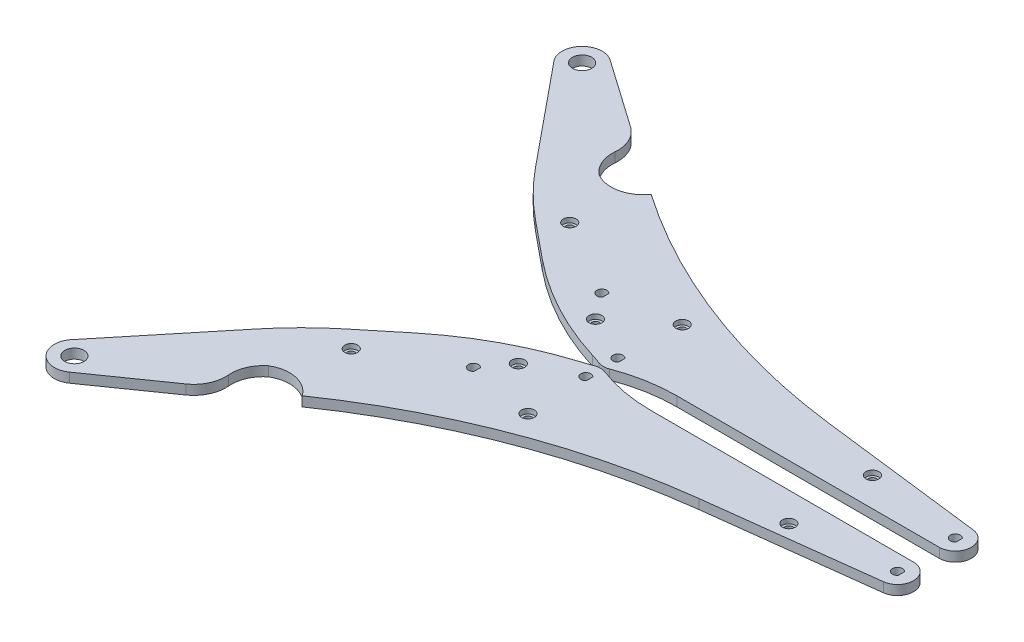
SolidWorks part; units mm, degrees
ref_plane "前视基准面" through (0, 0, 0) normal (0, 0, 1) x (1, 0, 0)
ref_plane "上视基准面" through (0, 0, 0) normal (0, 1, 0) x (1, 0, 0)
ref_plane "右视基准面" through (0, 0, 0) normal (1, 0, 0) x (0, 0, -1)
other "Configuration Table"
sketch "草图3" plane through (0, 0, 0) normal (0, 1, 0) x (1, 0, 0)
  line L0 (0, 0) -> (100, 0)
  line L1 (-82.5612, -80.1259) -> (0, -22.316)
  line L2 (-90.5752, -70.5752) -> (-141.151, -121.151) construction
  line L3 (100.6093, -9.9627) -> (0, -22.316)
  line L4 (-141.151, -121.151) -> (-82.5612, -80.1259) construction
  line L5 (100, 0) -> (181.7493, 0) construction
  line L6 (181.7493, 0) -> (100.6093, -9.9627) construction
  line L7 (101.2, -4.0189) -> (101.2, -5.9811)
  line L8 (-19.8, -15.0189) -> (-19.8, -16.9811)
  line L9 (0.2, -0.0189) -> (0.2, -1.9811)
  line L10 (-20, 0) -> (-90.5752, -70.5752)
  line L11 (-53.0717, -59.4772) -> (-58.8074, -51.2857)
  line L12 (0, 0) -> (-20, 0)
  line L13 (-58.8074, -51.2857) -> (-45.701, -42.1085)
  line L14 (-45.701, -42.1085) -> (-39.9652, -50.3)
  line L16 (-90.5752, -70.5752) -> (-58.8231, -31.7521)
  line L17 (-58.8231, -31.7521) -> (-20, 0)
  circle A0 centre (100, -5) radius 1.55
  circle A1 centre (100, -5) radius 5
  circle A2 centre (-86.1504, -75) radius 6.2576
  circle A3 centre (-1, -1) radius 1.55
  circle A4 centre (-1, -1) radius 4.55
  circle A5 centre (-21, -16) radius 1.55
  circle A6 centre (-86.1504, -75) radius 3
  dimension "D2" = 10
  dimension "D3" = 3.1
  dimension "D10" = 75
  dimension "D11" = 3.1
  dimension "D12" = 3
  dimension "D13" = 3.1
  dimension "D16" = 6
  dimension "D1" = 100
  dimension "D4" = 7
  dimension "D5" = 135
  dimension "D6" = 20
  dimension "D7" = 10
  dimension "D8" = 1
  dimension "D9" = 1
  dimension "D14" = 15
  dimension "D15" = 20
  dimension "D17" = 1.2
  dimension "D18" = 1.2
  dimension "D19" = 1.2
  dimension "D20" = 10
  dimension "D21" = 16
  dimension "D22" = 36
  dimension "D23" = 5
extrude "凸台-拉伸1" add sketch "草图3" along normal blind 3 contours A4 L12 L10 A2 L1 L3 A1 L0 A5 | A2 A6 | L8 A5 | L0 A4 L12 A3 | L9 A3 | L12 A4 L0 A3 | A1 A0 | L7 A0 | L17 L16 L10 region at (-1, 0, -1.5321) region at (-1, 0, 2.6387) region at (-3.2868, 0, 23.095) region at (0.3414, 0, 1) region at (103.4355, 0, 1.5645) region at (-56.4661, 0, 34.1091) region at (-83.8234, 0, 69.3822) region at (101.3414, 0, 5) region at (-19.6586, 0, 16)
fillet "圆角1" radius 200 1 edges at (0, 1.5, 22.316)
fillet "圆角3" radius 50 2 edges at (3.4387, 1.5, 0) (-5.4387, 1.5, 0)
sketch "草图4" plane through (0, 3, 0) normal (0, 1, 0) x (1, 0, 0)
  circle A0 centre (70.2, -9) radius 2
  circle A1 centre (70.2, -9) radius 1.25
  circle A2 centre (0, -20) radius 2
  circle A3 centre (0, -20) radius 1.25
  circle A8 centre (-45, -30) radius 2
  circle A9 centre (-45, -30) radius 1.25
  circle A10 centre (-15, -8) radius 2
  circle A11 centre (-15, -8) radius 1.25
  dimension "D1" = 4
  dimension "D2" = 2.5
  dimension "D3" = 70
  dimension "D4" = 9
  dimension "D5" = 20
  dimension "D6" = 15
  dimension "D7" = 8
  dimension "D8" = 45
  dimension "D9" = 30
extrude "切除-拉伸1" cut sketch "草图4" against normal through all contours A1 | A3 | A11 | A9
extrude "切除-拉伸2" cut sketch "草图4<3>" against normal offset from surface (1.5 mm away) 1.5 contours A0 | A2 | A8 | A10 up to face at (70.2, 0, 10.25)
sketch "草图4<3>" plane through (0, 3, 0) normal (0, 1, 0) x (1, 0, 0) same geometry as "草图4"
fillet "圆角4" radius 10 1 edges at (-53.0717, 1.5, 59.4772)
fillet "圆角5" radius 10 2 edges at (-45.701, 1.5, 42.1085) (-58.8074, 1.5, 51.2857)
fillet "圆角6" radius 100 2 edges at (-20, 1.5, 0) (-58.8231, 1.5, 31.7521)
ref_plane "基准面1" through (0, 0, -4) normal (0, 0, 1) x (1, 0, 0)
mirror "镜向2" about plane through (0, 0, -4) normal (0, 0, 1) of bodies 127
